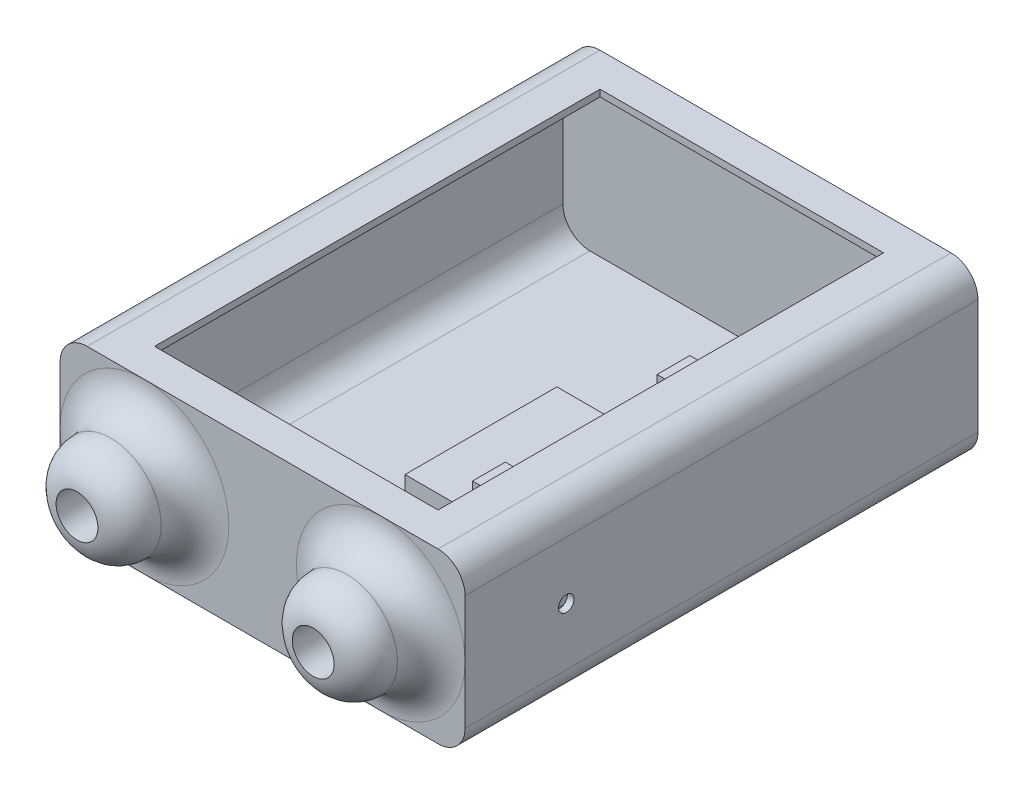
SolidWorks part; units mm, degrees
material "PLA Aero Bambu"
ref_plane "Front Plane" through (0, 0, 0) normal (0, 0, 1) x (1, 0, 0)
ref_plane "Top Plane" through (0, 0, 0) normal (0, 1, 0) x (1, 0, 0)
ref_plane "Right Plane" through (0, 0, 0) normal (1, 0, 0) x (0, 0, -1)
sketch "Sketch1" plane through (0, 0, 0) normal (0, 0, 1) x (1, 0, 0)
  line L1 (-30, 12.5) -> (30, 12.5)
  line L2 (-30, 12.5) -> (-30, -12.5)
  line L3 (-30, -12.5) -> (30, -12.5)
  line L4 (30, 12.5) -> (30, -12.5)
  line L5 (-30, 12.5) -> (30, -12.5) construction
  line L6 (-30, -12.5) -> (30, 12.5) construction
  point P0 (0, 0)
  dimension "D1" = 25
  dimension "D2" = 60
extrude "Boss-Extrude1" add sketch "Sketch1" against normal blind 1
sketch "Sketch2" plane through (0, 0, -1) normal (0, 0, -1) x (-1, 0, 0)
  line L0 (-30, 12.5) -> (-30, -12.5)
  line L1 (30, -12.5) -> (-30, -12.5) construction
  line L2 (-30, -12.5) -> (30, -12.5)
  line L3 (30, -12.5) -> (30, 12.5)
  line L4 (30, 12.5) -> (-30, 12.5)
  line L5 (29, 11.5) -> (-29, 11.5)
  line L6 (-29, 11.5) -> (-29, -11.5)
  line L7 (-29, -11.5) -> (29, -11.5)
  line L8 (29, -11.5) -> (29, 11.5)
  dimension "D1" = 1
extrude "Boss-Extrude2" add sketch "Sketch2" along normal blind 75
fillet "Fillet2" radius 4 8 edges at (30, 12.5, -38) (30, -12.5, -38) (-30, -12.5, -38) (-30, 12.5, -38) (-29, -11.5, -38.5) (-29, 11.5, -38.5) (29, 11.5, -38.5) (29, -11.5, -38.5)
sketch "Sketch4" plane through (0, 0, 0) normal (0, 0, 1) x (1, 0, 0)
  line L0 (-17.5, 0) -> (17.5, 0) construction
  circle A0 centre (-17.5, 0) radius 7.5
  circle A1 centre (-17.5, 0) radius 3.1
  circle A2 centre (17.5, 0) radius 3.1
  circle A3 centre (17.5, 0) radius 7.5
  point P5 (0, 0)
  dimension "D1" = 6.2
  dimension "D2" = 15
  dimension "D3" = 35
extrude "Boss-Extrude3" add sketch "Sketch4" along normal blind 10
fillet "Fillet3" radius 5 4 edges at (-10, 0, 0) (-10, 0, 10) (25, 0, 10) (25, 0, 0)
sketch "Sketch18" plane through (0, 0, 0) normal (0, 0, 1) x (1, 0, 0)
  circle A0 centre (-17.5, 0) radius 2
  circle A1 centre (17.5, 0) radius 2
  dimension "D1" = 4
extrude "Cut-Extrude6" cut sketch "Sketch18" against normal up to surface (1 mm away) up to face at (0, 0, -1)
sketch "Sketch5" plane through (30, 0, 0) normal (1, 0, 0) x (0, 0, -1)
  circle A0 centre (15, 0) radius 1.15
  dimension "D1" = 2.3
  dimension "D2" = 15
extrude "Cut-Extrude1" cut sketch "Sketch5" against normal through all contours A0
sketch "Sketch10" plane through (0, -11.5, 0) normal (0, 1, 0) x (1, 0, 0)
  line L0 (17.5, 0) -> (-17.5, 0) construction
  line L4 (26, 0) -> (26, 76) construction
  line L6 (-3.9968, 47.6018) -> (18.48, 47.6018)
  line L7 (-3.9968, 47.6018) -> (-3.9968, 25.1)
  line L8 (-3.9968, 25.1) -> (18.48, 25.1)
  line L9 (18.48, 47.6018) -> (18.48, 25.1)
  dimension "D1" = 25.1
  dimension "D2" = 7.52
  dimension "D3" = 22.5018
  dimension "D4" = 22.4768
extrude "Boss-Extrude4" add sketch "Sketch10" along normal blind 6
sketch "Sketch12" plane through (0, -11.5, 0) normal (0, 1, 0) x (1, 0, 0)
  line L5 (25, 1) -> (25, 76) construction
  line L10 (10.83, 25.1335) -> (13.33, 25.1335)
  line L12 (10.83, 25.1335) -> (10.83, 20.275)
  line L13 (10.83, 20.275) -> (13.33, 20.275)
  line L14 (13.33, 25.1335) -> (13.33, 20.275)
  line L15 (10.83, 47.6165) -> (13.33, 47.6165)
  line L16 (10.83, 47.6165) -> (10.83, 52.475)
  line L17 (10.83, 52.475) -> (13.33, 52.475)
  line L18 (13.33, 47.6165) -> (13.33, 52.475)
  dimension "D1" = 4.8585
  dimension "D4" = 2.5
  dimension "D5" = 11.67
  dimension "D6" = 22.483
  dimension "D7" = 20.275
extrude "Boss-Extrude5" add sketch "Sketch12" along normal blind 15
sketch "Sketch13" plane through (13.33, 0, 0) normal (1, 0, 0) x (0, 0, -1)
  circle A0 centre (22.7042, 0) radius 1.35
  circle A1 centre (50.0458, 0) radius 1.35
  dimension "D2" = 2.7
  dimension "D3" = 2.7
  dimension "D4" = 27.3415
  dimension "D1" = 22.7042
extrude "Cut-Extrude3" cut sketch "Sketch13" against normal blind 12
sketch "Sketch19" plane through (0, 12.5, 0) normal (0, 1, 0) x (1, 0, 0)
  line L0 (-26, 76) -> (-26, 0) construction
  line L1 (-21, 5) -> (21, 5)
  line L2 (-21, 5) -> (-21, 71)
  line L3 (-21, 71) -> (21, 71)
  line L4 (21, 5) -> (21, 71)
  line L5 (17.5, 0) -> (-17.5, 0) construction
  line L6 (-26, 76) -> (26, 76) construction
  point P6 (0, 5)
  dimension "D1" = 5
  dimension "D2" = 5
  dimension "D3" = 5
extrude "Cut-Extrude7" cut sketch "Sketch19" against normal up to surface (1 mm away) up to face at (0, 11.5, -38.5)
sketch "Sketch17" [suppressed] plane through (0, 0, -76) normal (0, 0, -1) x (-1, 0, 0)
  line L0 (20, 8.5) -> (-20, 8.5)
split "Split1" [suppressed] bodies to split 114
sketch "Sketch20" plane through (0, 0, -76) normal (0, 0, -1) x (-1, 0, 0)
  line L0 (-25, 11.5) -> (25, 11.5)
  line L1 (29, 7.5) -> (29, -7.5)
  line L2 (-25, -11.5) -> (25, -11.5)
  line L3 (-29, 7.5) -> (-29, -7.5)
  arc A0 (-29, 7.5) -> (-25, 11.5) centre (-25, 7.5) cw
  arc A1 (25, 11.5) -> (29, 7.5) centre (25, 7.5) cw
  arc A2 (25, -11.5) -> (29, -7.5) centre (25, -7.5) ccw construction
  arc A3 (25, -11.5) -> (29, -7.5) centre (25, -7.5) ccw construction
  arc A4 (29, -7.5) -> (25, -11.5) centre (25, -7.5) cw
  arc A5 (-25, -11.5) -> (-29, -7.5) centre (-25, -7.5) cw
extrude "Boss-Extrude7" add sketch "Sketch20" against normal blind 2.5
